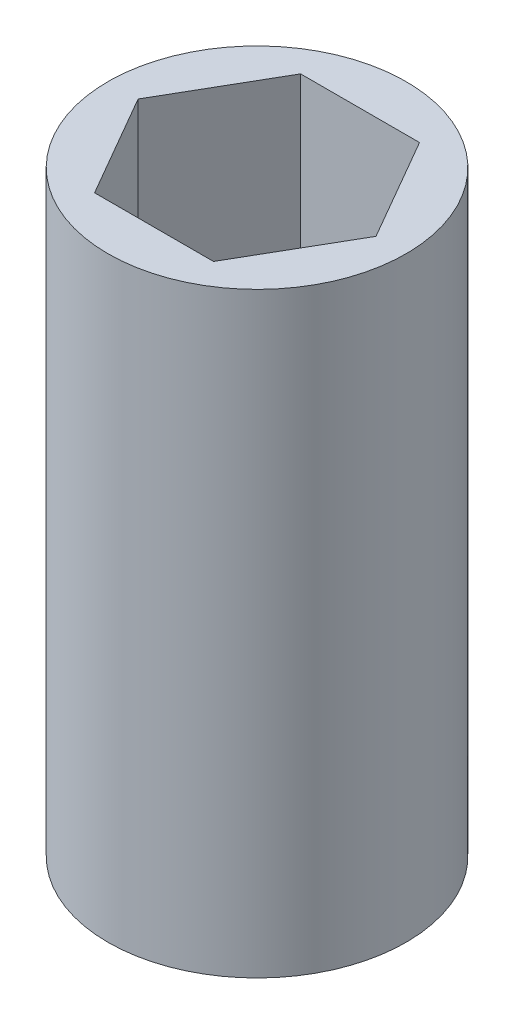
SolidWorks part; units mm, degrees
ref_plane "Front Plane" through (0, 0, 0) normal (0, 0, 1) x (1, 0, 0)
ref_plane "Top Plane" through (0, 0, 0) normal (0, 1, 0) x (1, 0, 0)
ref_plane "Right Plane" through (0, 0, 0) normal (1, 0, 0) x (0, 0, -1)
sketch "Sketch1" plane through (0, 0, 0) normal (0, 1, 0) x (1, 0, 0)
  line L1 (2.7863, -4.826) -> (5.5726, 0)
  line L2 (5.5726, 0) -> (2.7863, 4.826)
  line L3 (2.7863, 4.826) -> (-2.7863, 4.826)
  line L4 (-2.7863, 4.826) -> (-5.5726, 0)
  line L5 (-5.5726, 0) -> (-2.7863, -4.826)
  line L6 (-2.7863, -4.826) -> (2.7863, -4.826)
  circle A0 centre (0, 0) radius 6.985
  circle A1 centre (0, 0) radius 4.826 construction
  dimension "D1" = 9.652
  dimension "D2" = 13.97
extrude "Boss-Extrude1" add sketch "Sketch1" along normal blind 27.94
